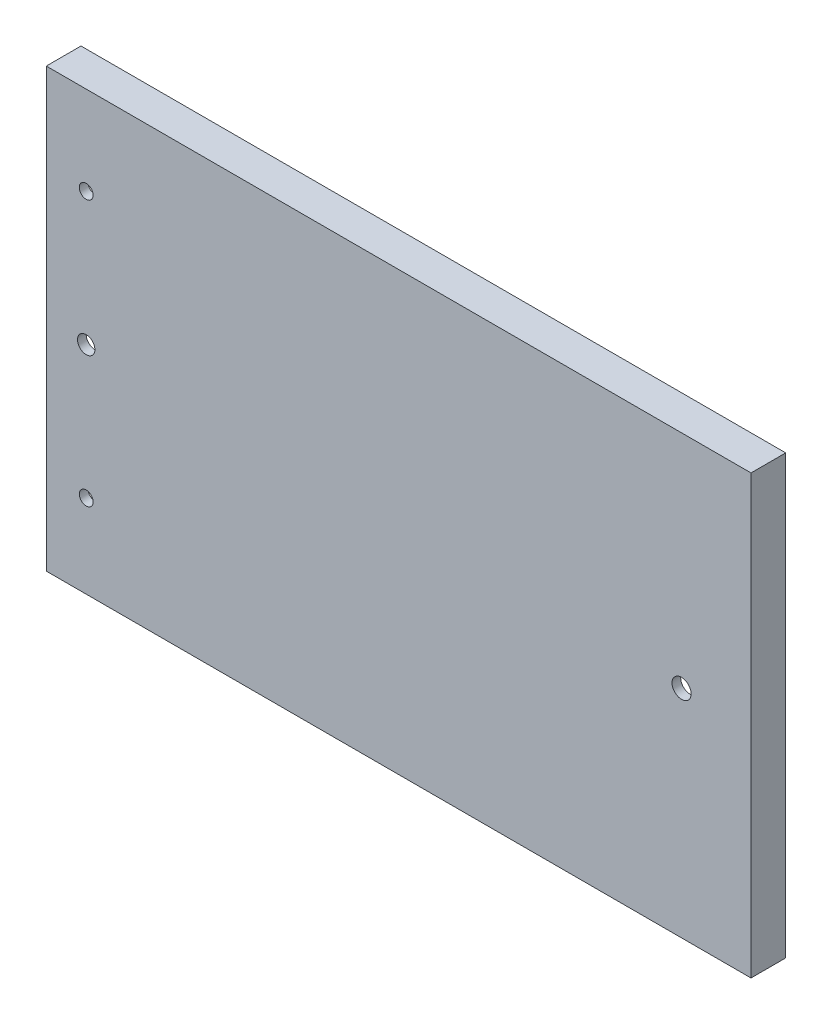
SolidWorks part; units mm, degrees
material "Настроенная пользователем пластмасса"
ref_plane "Спереди" through (0, 0, 0) normal (0, 0, 1) x (1, 0, 0)
ref_plane "Сверху" through (0, 0, 0) normal (0, 1, 0) x (1, 0, 0)
ref_plane "Справа" through (0, 0, 0) normal (1, 0, 0) x (0, 0, -1)
ref_plane "Плоскость4" through (0, 0, 0) normal (0, 0, -1) x (-1, 0, 0)
sketch "Эскиз1" plane through (0, 0, 0) normal (0, 0, -1) x (-1, 0, 0)
  line L0 (0, 252) -> (-406, 252)
  line L1 (-406, 252) -> (-406, 0)
  line L2 (-406, 0) -> (0, 0)
  line L3 (0, 0) -> (0, 252)
  dimension "D1" = 252
extrude "Бобышка-Вытянуть1" add sketch "Эскиз1" against normal blind 20
sketch "Эскиз2" plane through (0, 0, 0) normal (0, 0, -1) x (-1, 0, 0)
  line L0 (-388, 244) -> (-388, 8)
  line L1 (-388, 8) -> (-3, 8)
  line L2 (-3, 8) -> (-3, 244)
  line L3 (-3, 244) -> (-388, 244)
  line L4 (0, 252) -> (-406, 252) construction
  line L5 (-406, 0) -> (0, 0) construction
  dimension "D1" = 8
  dimension "D2" = 8
extrude "Вырез-Вытянуть1" cut sketch "Эскиз2" against normal blind 15
hole_wizard "Диаметр отверстия Ø10.0 (10)1" positions "Эскиз4" profile "Эскиз3" hole size "Ø10.0" standard "Ansi Metric"
sketch "Эскиз4" plane through (0, 0, 15) normal (0, 0, -1) x (-1, 0, 0)
  point P0 (-23, 124.5)
sketch "Эскиз3" plane through (23, 124.5, 15) normal (1, 0, 0) x (0, 1, 0)
  line L0 (0, 0) -> (0, 5)
  line L1 (0, 5) -> (5, 5)
  line L2 (5, 5) -> (5, 0)
  line L5 (5, 0) -> (0, 0)
  line L11 (0, -6.35) -> (0, 107.95) construction
  dimension "Диаметр сквозного отверстия" = 10
  dimension "Глубина сквозного отверстия" = 5
hole_wizard "Диаметр отверстия Ø8.0 (8)1" positions "Эскиз6" profile "Эскиз5" hole size "Ø8.0" standard "Ansi Metric"
sketch "Эскиз6" plane through (0, 0, 15) normal (0, 0, -1) x (-1, 0, 0)
  point P0 (-23, 201)
  point P1 (-23, 48)
sketch "Эскиз5" plane through (23, 201, 15) normal (1, 0, 0) x (0, 1, 0)
  line L0 (0, 0) -> (0, 5)
  line L1 (0, 5) -> (4, 5)
  line L2 (4, 5) -> (4, 0)
  line L5 (4, 0) -> (0, 0)
  line L11 (0, -6.35) -> (0, 107.95) construction
  dimension "Диаметр сквозного отверстия" = 8
  dimension "Глубина сквозного отверстия" = 5
hole_wizard "Диаметр отверстия Ø11.0 (11)1" positions "Эскиз8" profile "Эскиз7" hole size "Ø11.0" standard "Ansi Metric"
sketch "Эскиз8" plane through (0, 0, 15) normal (0, 0, -1) x (-1, 0, 0)
  point P0 (-366, 124.5)
sketch "Эскиз7" plane through (366, 124.5, 15) normal (1, 0, 0) x (0, 1, 0)
  line L0 (0, 0) -> (0, 5)
  line L1 (0, 5) -> (5.5, 5)
  line L2 (5.5, 5) -> (5.5, 0)
  line L5 (5.5, 0) -> (0, 0)
  line L11 (0, -6.35) -> (0, 107.95) construction
  dimension "Диаметр сквозного отверстия" = 11
  dimension "Глубина сквозного отверстия" = 5
